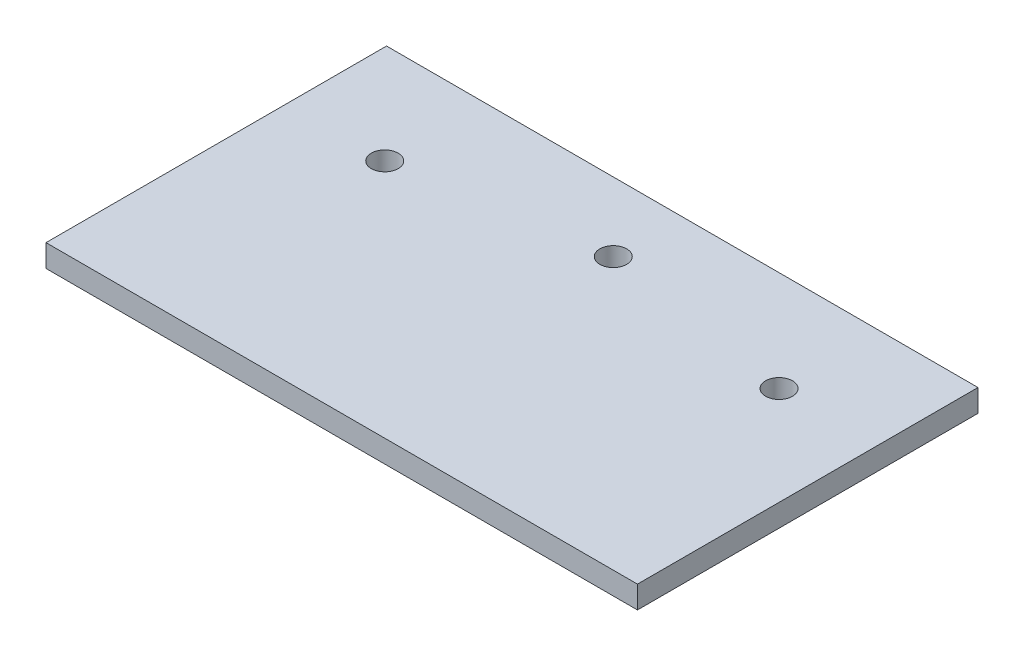
SolidWorks part; units mm, degrees
ref_plane "Front Plane" through (0, 0, 0) normal (0, 0, 1) x (1, 0, 0)
ref_plane "Top Plane" through (0, 0, 0) normal (0, 1, 0) x (1, 0, 0)
ref_plane "Right Plane" through (0, 0, 0) normal (1, 0, 0) x (0, 0, -1)
sketch "Sketch1" plane through (0, 0, 0) normal (0, 1, 0) x (1, 0, 0)
  line L0 (0, 3) -> (66, 3) construction
  line L1 (0, 0) -> (66, 0)
  line L2 (0, 0) -> (0, 38)
  line L3 (0, 38) -> (66, 38)
  line L4 (66, 0) -> (66, 38)
  line L5 (0, 22.8) -> (66, 22.8) construction
  line L6 (0, 28.3) -> (66, 28.3) construction
  line L7 (0, 31.8) -> (66, 31.8) construction
  dimension "D1" = 66
  dimension "D2" = 3
  dimension "D3" = 19.8
  dimension "D4" = 25.3
  dimension "D5" = 28.8
  dimension "D6" = 35
extrude "Boss-Extrude1" add sketch "Sketch1" along normal blind 2.5 contours L3 L4 L1 L2
sketch "Sketch2" plane through (0, 0, 0) normal (0, -1, 0) x (1, 0, 0)
  line L0 (33, 0) -> (33, -38) construction
  line L1 (0, 0) -> (66, 0) construction
  line L7 (0, -38) -> (66, -38) construction
  line L8 (0, -31.8) -> (66, -31.8) construction
  line L9 (0, -28.3) -> (66, -28.3) construction
  circle A0 centre (33, -30.3) radius 1.5
  circle A1 centre (11, -26.8) radius 1.5
  circle A2 centre (55, -26.8) radius 1.5
  dimension "D1" = 3
  dimension "D4" = 3
  dimension "D2" = 1.5
  dimension "D3" = 22
  dimension "D5" = 1.5
extrude "Cut-Extrude1" cut sketch "Sketch2" against normal through all
